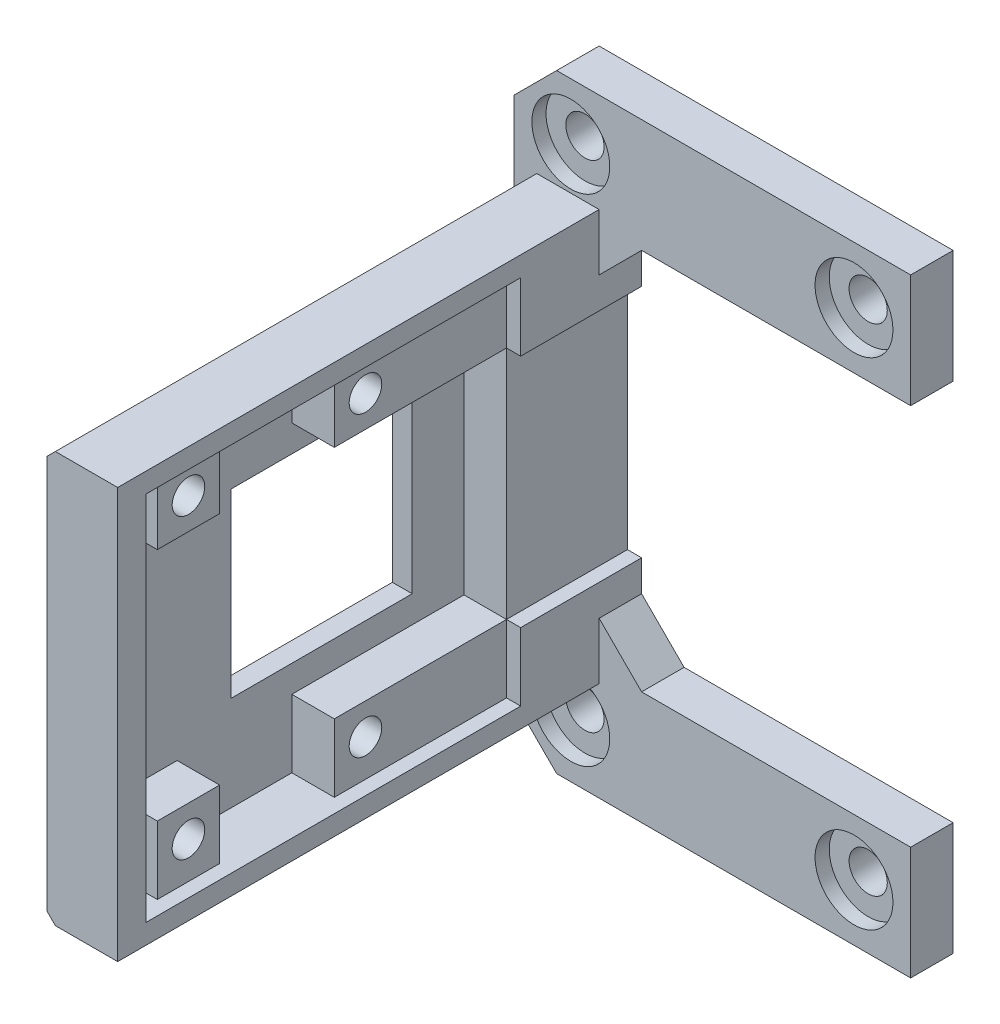
SolidWorks part; units mm, degrees
note: The reader was unsure of these and kept them because the rebuilt part matched: shared geometry of "Sketch11<3>".
ref_plane "Front Plane" through (0, 0, 0) normal (0, 0, 1) x (1, 0, 0)
ref_plane "Top Plane" through (0, 0, 0) normal (0, 1, 0) x (1, 0, 0)
ref_plane "Right Plane" through (0, 0, 0) normal (1, 0, 0) x (0, 0, -1)
sketch "Sketch1" plane through (0, 0, 0) normal (0, 0, 1) x (1, 0, 0)
  line L0 (-37, 11) -> (-42, 11) construction
  line L1 (-42, -11) -> (-37, -11) construction
  line L2 (-37, 11) -> (-42, 11)
  line L3 (-42, -11) -> (-37, -11)
  circle A0 centre (-41, -17.5) radius 2.05 construction
  circle A1 centre (-41, 17.5) radius 2.05 construction
  circle A2 centre (-61, 17.5) radius 2.05 construction
  circle A3 centre (-61, -17.5) radius 2.05 construction
  circle A4 centre (-41, -17.5) radius 2.05
  circle A5 centre (-41, 17.5) radius 2.05
  circle A6 centre (-61, 17.5) radius 2.05
  circle A7 centre (-61, -17.5) radius 2.05
sketch "Sketch2" plane through (0, 0, 0) normal (0, 0, 1) x (1, 0, 0)
  line L0 (-65, 21.5) -> (-37, 21.5)
  line L1 (-37, 21.5) -> (-37, 13.5)
  line L2 (-37, 13.5) -> (-59, 13.5)
  line L4 (-65, 21.5) -> (-65, -21.5)
  line L5 (-65, -21.5) -> (-37, -21.5)
  line L6 (-37, -21.5) -> (-37, -13.5)
  line L7 (-37, -13.5) -> (-59, -13.5)
  line L10 (-61, 17.5) -> (-61, 21.5) construction
  line L11 (-61, -17.5) -> (-61, -21.5) construction
  line L12 (-59, 13.5) -> (-59, -13.5)
  dimension "D1" = 4
  dimension "D2" = 4
  dimension "D3" = 4
  dimension "D4" = 22
extrude "Boss-Extrude1" add sketch "Sketch2" along normal blind 3
sketch "Sketch3" plane through (0, 0, 3) normal (0, 0, 1) x (1, 0, 0)
  circle A0 centre (-41, 17.5) radius 1.35
  circle A1 centre (-61, 17.5) radius 1.35
  circle A2 centre (-61, -17.5) radius 1.35
  circle A3 centre (-41, -17.5) radius 1.35
  dimension "D1" = 2.7
extrude "Cut-Extrude1" cut sketch "Sketch3" against normal through all
sketch "Sketch4" plane through (0, 0, 3) normal (0, 0, 1) x (1, 0, 0)
  line L0 (-37, -13.5) -> (-59, -13.5) construction
  line L1 (-59, 13.5) -> (-65, 13.5)
  line L2 (-59, 13.5) -> (-59, -13.5)
  line L3 (-59, -13.5) -> (-65, -13.5)
  line L4 (-65, 13.5) -> (-65, -13.5)
  line L5 (-65, 21.5) -> (-65, -21.5) construction
extrude "Boss-Extrude2" add sketch "Sketch4" along normal blind 32
sketch "Sketch5" plane through (-65, 0, 0) normal (-1, 0, 0) x (0, 0, 1)
  circle A0 centre (23, 0) radius 9
  dimension "D1" = 18
  dimension "D2" = 23
extrude "Cut-Extrude2" cut sketch "Sketch5" against normal through all
sketch "Sketch6" plane through (-59, 0, 0) normal (1, 0, 0) x (0, 0, -1)
  line L1 (-27, -12.5) -> (-19, -12.5)
  line L2 (-27, -12.5) -> (-27, 12.5)
  line L3 (-27, 12.5) -> (-19, 12.5)
  line L4 (-19, -12.5) -> (-19, 12.5)
  line L5 (-27, -12.5) -> (-19, 12.5) construction
  line L6 (-27, 12.5) -> (-19, -12.5) construction
  point P0 (-23, 0)
  dimension "D1" = 25
  dimension "D2" = 8
extrude "Cut-Extrude3" cut sketch "Sketch6" against normal blind 3
sketch "Sketch7" plane through (-59, 0, 0) normal (1, 0, 0) x (0, 0, -1)
  circle A4 centre (-30, 10.5) radius 1 construction
  circle A5 centre (-16, 10.5) radius 1 construction
  circle A6 centre (-16, -10.5) radius 1 construction
  circle A7 centre (-30, -10.5) radius 1 construction
  circle A8 centre (-30, 10.5) radius 2.5
  circle A9 centre (-16, 10.5) radius 2.5
  circle A10 centre (-16, -10.5) radius 2.5
  circle A11 centre (-30, -10.5) radius 2.5
  circle A12 centre (-30, 10.5) radius 1.65
  circle A13 centre (-16, 10.5) radius 1.65
  circle A14 centre (-16, -10.5) radius 1.65
  circle A15 centre (-30, -10.5) radius 1.65
  dimension "D1" = 5
  dimension "D2" = 3.3
extrude "Boss-Extrude3" add sketch "Sketch7" along normal blind 3
sketch "Sketch8" plane through (-59, 0, 0) normal (1, 0, 0) x (0, 0, -1)
  circle A0 centre (-30, -10.5) radius 1.65 construction
  circle A1 centre (-16, -10.5) radius 1.65 construction
  circle A2 centre (-16, 10.5) radius 1.65 construction
  circle A3 centre (-30, 10.5) radius 1.65 construction
  circle A4 centre (-30, -10.5) radius 1.65
  circle A5 centre (-16, -10.5) radius 1.65
  circle A6 centre (-16, 10.5) radius 1.65
  circle A7 centre (-30, 10.5) radius 1.65
extrude "Cut-Extrude4" cut sketch "Sketch8" against normal blind 3
chamfer "Chamfer1" distance 0.6 angle 45 3 edges at (-65, -13.5, 19) (-65, 13.5, 19) (-65, 0, 35)
sketch "Sketch9" plane through (0, 0, 3) normal (0, 0, 1) x (1, 0, 0)
  circle A0 centre (-61, 17.5) radius 2.75
  circle A1 centre (-41, 17.5) radius 2.75
  circle A2 centre (-41, -17.5) radius 2.75
  circle A3 centre (-61, -17.5) radius 2.75
  dimension "D1" = 5.5
extrude "Cut-Extrude5" cut sketch "Sketch9" against normal blind 1
chamfer "Chamfer2" distance 3 angle 45 2 edges at (-59, 13.5, 1.5) (-59, -13.5, 1.5)
chamfer "Chamfer3" distance 3 angle 45 2 edges at (-65, 21.5, 1.5) (-65, -21.5, 1.5)
sketch "Sketch10" plane through (-59, 0, 0) normal (1, 0, 0) x (0, 0, -1)
  line L1 (-35, 13.5) -> (-3, 13.5)
  line L2 (-35, 13.5) -> (-35, -13.5)
  line L3 (-35, -13.5) -> (-3, -13.5)
  line L4 (-3, 13.5) -> (-3, -13.5)
extrude "Cut-Extrude6" cut sketch "Sketch10" along normal blind 20
sketch "Sketch11" plane through (-59, 0, 0) normal (1, 0, 0) x (0, 0, -1)
  line L0 (-27, -8.0623) -> (-27, -12.5) construction
  line L1 (-27, -12.5) -> (-19, -12.5) construction
  line L2 (-19, -12.5) -> (-19, -8.0623) construction
  line L3 (-19, 8.0623) -> (-19, 12.5) construction
  line L4 (-19, 12.5) -> (-27, 12.5) construction
  line L5 (-27, 12.5) -> (-27, 8.0623) construction
  line L6 (-27, -8.0623) -> (-27, -12.5)
  line L7 (-27, -12.5) -> (-19, -12.5)
  line L8 (-19, -12.5) -> (-19, -8.0623)
  line L9 (-19, 8.0623) -> (-19, 12.5)
  line L10 (-19, 12.5) -> (-27, 12.5)
  line L11 (-27, 12.5) -> (-27, 8.0623)
  circle A0 centre (-30, -10.5) radius 1.65 construction
  circle A2 centre (-16, -10.5) radius 1.65 construction
  circle A3 centre (-16, 10.5) radius 1.65 construction
  arc A5 (-27, 8.0623) -> (-27, -8.0623) centre (-23, 0) ccw construction
  arc A6 (-19, -8.0623) -> (-19, 8.0623) centre (-23, 0) ccw construction
  circle A7 centre (-30, 10.5) radius 1.65 construction
  circle A8 centre (-30, -10.5) radius 1.65
  circle A10 centre (-16, -10.5) radius 1.65
  circle A11 centre (-16, 10.5) radius 1.65
  arc A13 (-27, 8.0623) -> (-27, -8.0623) centre (-23, 0) ccw
  arc A14 (-19, -8.0623) -> (-19, 8.0623) centre (-23, 0) ccw
  circle A15 centre (-30, 10.5) radius 1.65
  circle M17 centre (-30, -10.5) radius 1.65
  circle M18 centre (-16, -10.5) radius 1.65
  circle M19 centre (-16, 10.5) radius 1.65
  circle M20 centre (-30, 10.5) radius 1.65
extrude "Boss-Extrude5" add sketch "Sketch11" against normal up to surface (3 mm away) contours M20 | M19 | M18 | M17 up to face at (-62, -10.5, 28.35)
extrude "Boss-Extrude6" add sketch "Sketch11<3>" against normal up to surface (3 mm away)
sketch "Sketch11<3>" plane through (-59, 0, 0) normal (1, 0, 0) x (0, 0, -1) same geometry as "Sketch11"
sketch "Sketch12" plane through (-62, 0, 0) normal (-1, 0, 0) x (0, 0, 1)
  circle A1 centre (23, 0) radius 9
  circle A2 centre (23, 0) radius 9
  dimension "D1" = 0
extrude "Boss-Extrude7" add sketch "Sketch12" along normal up to surface (3 mm away) up to face at (-65, -9, 23)
sketch "Sketch14" plane through (-59, 0, 0) normal (1, 0, 0) x (0, 0, -1)
  line L0 (-33, 0) -> (-9.14, 0) construction
  line L1 (-33, -12.5) -> (-9.14, -12.5)
  line L2 (-33, -12.5) -> (-33, 12.5)
  line L3 (-33, 12.5) -> (-9.14, 12.5)
  line L4 (-9.14, -12.5) -> (-9.14, 12.5)
  line L5 (-33, -12.5) -> (-9.14, 12.5) construction
  line L6 (-33, 12.5) -> (-9.14, -12.5) construction
  line L7 (-35, -13.5) -> (-35, 13.5) construction
  line L8 (-24, -5.4) -> (-13.2, -5.4)
  line L9 (-24, -5.4) -> (-24, 5.4)
  line L10 (-24, 5.4) -> (-13.2, 5.4)
  line L11 (-13.2, -5.4) -> (-13.2, 5.4)
  line L12 (-24, -5.4) -> (-13.2, 5.4) construction
  line L13 (-24, 5.4) -> (-13.2, -5.4) construction
  line L14 (-31, -10.5) -> (-18.5, -10.5)
  line L15 (-31, -10.5) -> (-31, 10.5)
  line L16 (-31, 10.5) -> (-18.5, 10.5)
  line L17 (-18.5, -10.5) -> (-18.5, 10.5)
  line L18 (-31, -10.5) -> (-18.5, 10.5) construction
  line L19 (-31, 10.5) -> (-18.5, -10.5) construction
  circle A0 centre (-31, 10.5) radius 1.1
  circle A1 centre (-18.5, 10.5) radius 1.1
  circle A2 centre (-18.5, -10.5) radius 1.1
  circle A3 centre (-31, -10.5) radius 1.1
  point P0 (-21.07, 0)
  point P5 (-9.14, 0)
  point P9 (-18.6, 0)
  point P14 (-24.75, 0)
  dimension "D8" = 2.2
  dimension "D1" = 23.86
  dimension "D2" = 25
  dimension "D3" = 10.8
  dimension "D4" = 14.4
  dimension "D5" = 2
  dimension "D6" = 2
  dimension "D7" = 14.5
  dimension "D9" = 2
sketch "Sketch15" plane through (-59, 0, 0) normal (1, 0, 0) x (0, 0, -1)
  line L8 (-33.6, 13.1) -> (-33.6, -13.1)
  line L9 (-33.6, -13.1) -> (-8.54, -13.1)
  line L10 (-8.54, -13.1) -> (-8.54, 13.1)
  line L11 (-8.54, 13.1) -> (-33.6, 13.1)
  line L12 (-33.6, 13.1) -> (-33.6, -13.1)
  line L13 (-33.6, -13.1) -> (-8.54, -13.1)
  line L14 (-8.54, -13.1) -> (-8.54, 13.1)
  line L15 (-8.54, 13.1) -> (-33.6, 13.1)
  dimension "D1" = 0.6
extrude "Cut-Extrude7" cut sketch "Sketch15" against normal offset from surface (4 mm away) 2 up to face at (-65, 0, 10.25)
sketch "Sketch16" plane through (-63, 0, 0) normal (1, 0, 0) x (0, 0, -1)
  line L8 (-25, -6.4) -> (-12.2, -6.4)
  line L9 (-12.2, -6.4) -> (-12.2, 6.4)
  line L10 (-12.2, 6.4) -> (-25, 6.4)
  line L11 (-25, 6.4) -> (-25, -6.4)
  line L12 (-25, -6.4) -> (-12.2, -6.4)
  line L13 (-12.2, -6.4) -> (-12.2, 6.4)
  line L14 (-12.2, 6.4) -> (-25, 6.4)
  line L15 (-25, 6.4) -> (-25, -6.4)
  dimension "D1" = 1
extrude "Cut-Extrude8" cut sketch "Sketch16" against normal through all
sketch "Sketch17" plane through (-63, 0, 0) normal (1, 0, 0) x (0, 0, -1)
  line L0 (-33.6, -13.1) -> (-8.54, -13.1) construction
  line L1 (-8.54, -13.1) -> (-20.7, -13.1)
  line L2 (-8.54, -13.1) -> (-8.54, -8.3)
  line L3 (-8.54, -8.3) -> (-20.7, -8.3)
  line L4 (-20.7, -13.1) -> (-20.7, -8.3)
  line L5 (-28.8, -13.1) -> (-33.2, -13.1)
  line L6 (-28.8, -13.1) -> (-28.8, -8.3)
  line L7 (-28.8, -8.3) -> (-33.2, -8.3)
  line L8 (-33.2, -13.1) -> (-33.2, -8.3)
  line L9 (-33.6, 0) -> (-8.54, 0) construction
  line L10 (-33.6, -13.1) -> (-33.6, 13.1) construction
  line L11 (-8.54, -13.1) -> (-8.54, 13.1) construction
  line L12 (-33.2, 13.1) -> (-33.2, 8.3)
  line L13 (-28.8, 8.3) -> (-33.2, 8.3)
  line L14 (-28.8, 13.1) -> (-28.8, 8.3)
  line L15 (-28.8, 13.1) -> (-33.2, 13.1)
  line L16 (-20.7, 13.1) -> (-20.7, 8.3)
  line L17 (-8.54, 8.3) -> (-20.7, 8.3)
  line L18 (-8.54, 13.1) -> (-8.54, 8.3)
  line L19 (-8.54, 13.1) -> (-20.7, 13.1)
  circle A0 centre (-31, -10.5) radius 1.1 construction
  circle A1 centre (-18.5, -10.5) radius 1.1 construction
  circle A2 centre (-31, 10.5) radius 1.1 construction
  circle A3 centre (-18.5, 10.5) radius 1.1 construction
  circle A4 centre (-31, -10.5) radius 1.1 construction
  circle A5 centre (-18.5, -10.5) radius 1.1 construction
  circle A6 centre (-31, 10.5) radius 1.1 construction
  circle A7 centre (-18.5, 10.5) radius 1.1 construction
  circle A8 centre (-18.5, 10.5) radius 1.1 construction
  circle A9 centre (-31, 10.5) radius 1.1 construction
  dimension "D3" = 2.2
  dimension "D1" = 2.2
  dimension "D2" = 2.2
  dimension "D4" = 2.2
  dimension "D5" = 2.2
extrude "Boss-Extrude8" add sketch "Sketch17" along normal blind 3
sketch "Sketch18" plane through (-60, 0, 0) normal (1, 0, 0) x (0, 0, -1)
  circle A0 centre (-18.5, -10.5) radius 1.1 construction
  circle A1 centre (-31, -10.5) radius 1.1 construction
  circle A2 centre (-18.5, 10.5) radius 1.1 construction
  circle A3 centre (-31, 10.5) radius 1.1 construction
  circle A4 centre (-18.5, -10.5) radius 1.1 construction
  circle A5 centre (-31, -10.5) radius 1.1 construction
  circle A6 centre (-18.5, 10.5) radius 1.1 construction
  circle A7 centre (-31, 10.5) radius 1.1 construction
  circle A8 centre (-31, 10.5) radius 1.15
  circle A9 centre (-18.5, 10.5) radius 1.15
  circle A10 centre (-18.5, -10.5) radius 1.15
  circle A11 centre (-31, -10.5) radius 1.15
  dimension "D1" = 2.3
extrude "Cut-Extrude9" cut sketch "Sketch18" against normal through all
sketch "Sketch19" plane through (-65, 0, 0) normal (-1, 0, 0) x (0, 0, 1)
  circle A0 centre (18.5, 10.5) radius 2
  circle A1 centre (31, 10.5) radius 2
  circle A2 centre (31, -10.5) radius 2
  circle A3 centre (18.5, -10.5) radius 2
  dimension "D1" = 4
extrude "Cut-Extrude11" cut sketch "Sketch19" against normal blind 1.8
sketch "Sketch20" plane through (-63.2, 0, 0) normal (-1, 0, 0) x (0, 0, 1)
  line L2 (17.35, 8.8637) -> (17.35, 12.1363)
  line L4 (19.65, 8.8637) -> (19.65, 12.1363)
  line L5 (17.35, 8.8637) -> (19.65, 12.1363) construction
  line L6 (17.35, 12.1363) -> (19.65, 8.8637) construction
  line L8 (29.85, 8.8637) -> (29.85, 12.1363)
  line L10 (32.15, 8.8637) -> (32.15, 12.1363)
  line L11 (29.85, 8.8637) -> (32.15, 12.1363) construction
  line L12 (29.85, 12.1363) -> (32.15, 8.8637) construction
  circle A0 centre (18.5, 10.5) radius 2 construction
  circle A1 centre (31, 10.5) radius 2 construction
  circle A2 centre (31, 10.5) radius 2 construction
  circle A3 centre (18.5, 10.5) radius 2 construction
  arc A4 (32.15, 12.1363) -> (29.85, 12.1363) centre (31, 10.5) ccw
  arc A5 (19.65, 12.1363) -> (17.35, 12.1363) centre (18.5, 10.5) ccw
  circle A6 centre (18.5, 10.5) radius 1.15 construction
  circle A7 centre (31, 10.5) radius 1.15 construction
  arc A8 (17.35, 8.8637) -> (19.65, 8.8637) centre (18.5, 10.5) ccw
  arc A9 (29.85, 8.8637) -> (32.15, 8.8637) centre (31, 10.5) ccw
  point P0 (18.5, 10.5)
  point P8 (31, 10.5)
extrude "Cut-Extrude13" cut sketch "Sketch20" against normal blind 0.2
sketch "Sketch21" plane through (-63, 0, 0) normal (-1, 0, 0) x (0, 0, 1)
  line L0 (19.65, 10.5) -> (19.65, 12.1363) construction
  line L1 (17.35, 9.35) -> (19.65, 9.35)
  line L2 (17.35, 9.35) -> (17.35, 11.65)
  line L3 (17.35, 11.65) -> (19.65, 11.65)
  line L4 (19.65, 9.35) -> (19.65, 11.65)
  line L5 (17.35, 9.35) -> (19.65, 11.65) construction
  line L6 (17.35, 11.65) -> (19.65, 9.35) construction
  line L7 (32.15, 10.5) -> (32.15, 12.1363) construction
  line L8 (29.85, 9.35) -> (32.15, 9.35)
  line L9 (29.85, 9.35) -> (29.85, 11.65)
  line L10 (29.85, 11.65) -> (32.15, 11.65)
  line L11 (32.15, 9.35) -> (32.15, 11.65)
  line L12 (29.85, 9.35) -> (32.15, 11.65) construction
  line L13 (29.85, 11.65) -> (32.15, 9.35) construction
  point P0 (18.5, 10.5)
  point P8 (31, 10.5)
extrude "Cut-Extrude14" cut sketch "Sketch21" against normal blind 0.2
mirror "Mirror1" about plane through (0, 0, 0) normal (0, 1, 0) of "Cut-Extrude14", "Cut-Extrude13"
chamfer "Chamfer4" distance 0.6 angle 45 4 edges at (-65, 0, 12.2) (-65, -6.4, 18.6) (-65, 0, 25) (-65, 6.4, 18.6)
sketch "Sketch22" plane through (-59, 0, 0) normal (1, 0, 0) x (0, 0, -1)
  line L0 (-35, -13.5) -> (-35, 13.5) construction
  line L1 (-33.6, 13.1) -> (-35, 13.1)
  line L2 (-33.6, 13.1) -> (-33.6, -13.1)
  line L3 (-33.6, -13.1) -> (-35, -13.1)
  line L4 (-35, 13.1) -> (-35, -13.1)
  line L5 (-33.2, -13.1) -> (-33.6, -13.1) construction
extrude "Cut-Extrude15" cut sketch "Sketch22" against normal up to surface (4 mm away) up to face at (-63, 0, 18.6)
sketch "Sketch23" plane through (0, 0, 35) normal (0, 0, 1) x (1, 0, 0)
  line L0 (-64.4, 13.5) -> (-63.4, 14.5)
  line L1 (-63.4, 14.5) -> (-59, 14.5)
  line L2 (-59, 14.5) -> (-59, 13.5)
  line L3 (-59, 13.5) -> (-64.4, 13.5)
  line L4 (-59, 10.5) -> (-59, 13.5) construction
  line L5 (-65, 12.9) -> (-64.4, 13.5) construction
  line L6 (-63, 0) -> (-28.9648, 0) construction
  line L8 (-59, -13.5) -> (-64.4, -13.5)
  line L9 (-59, -14.5) -> (-59, -13.5)
  line L10 (-63.4, -14.5) -> (-59, -14.5)
  line L11 (-64.4, -13.5) -> (-63.4, -14.5)
  line L12 (-63, -13.1) -> (-63, 13.1) construction
  point P12 (0, 0)
  point P19 (0, 0)
  dimension "D1" = 1
extrude "Boss-Extrude9" add sketch "Sketch23" against normal up to surface (32 mm away) up to face at (-56.0444, 15.4333, 3)
sketch "Sketch24" plane through (-59, 0, 0) normal (1, 0, 0) x (0, 0, -1)
  line L0 (-8.54, -13.1) -> (-8.54, 13.1) construction
  line L1 (-8.54, 8.3) -> (0, 8.3)
  line L2 (-8.54, 8.3) -> (-8.54, -8.3)
  line L3 (-8.54, -8.3) -> (0, -8.3)
  line L4 (0, 8.3) -> (0, -8.3)
  line L5 (-20.7, 8.3) -> (-8.54, 8.3) construction
  line L6 (-8.54, -8.3) -> (-20.7, -8.3) construction
  line L7 (0, -10.5) -> (0, 10.5) construction
extrude "Cut-Extrude16" cut sketch "Sketch24" against normal up to surface (1 mm away) up to face at (-60, 10.5, 17.35)
sketch "Sketch27" plane through (0, 0, 35) normal (0, 0, 1) x (1, 0, 0)
  line L0 (-59, 14.5) -> (-63.4, 14.5)
  line L1 (-63.4, 14.5) -> (-65, 12.9)
  line L2 (-65, 12.9) -> (-65, -12.9)
  line L3 (-65, -12.9) -> (-63.4, -14.5)
  line L4 (-63.4, -14.5) -> (-59, -14.5)
  line L5 (-59, -14.5) -> (-59, 14.5)
extrude "Boss-Extrude10" add sketch "Sketch27" along normal blind 2
chamfer "Chamfer5" distance 1 angle 45 1 edges at (-65, 0, 37)
